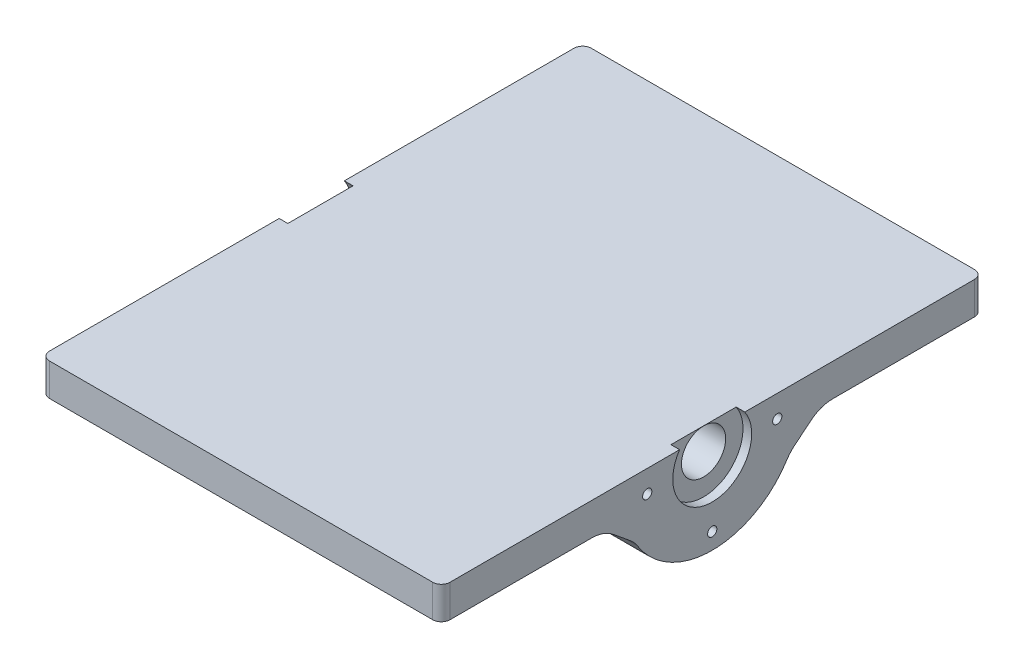
SolidWorks part; units mm, degrees
material "Copper"
ref_plane "Front Plane" through (0, 0, 0) normal (0, 0, 1) x (1, 0, 0)
ref_plane "Top Plane" through (0, 0, 0) normal (0, 1, 0) x (1, 0, 0)
ref_plane "Right Plane" through (0, 0, 0) normal (1, 0, 0) x (0, 0, -1)
sketch "Sketch1" plane through (0, 0, 0) normal (0, 0, 1) x (1, 0, 0)
  line L1 (0, 0) -> (-117.348, 0)
  line L2 (0, 0) -> (0, -38.1)
  line L3 (0, -38.1) -> (-117.348, -38.1)
  line L4 (-117.348, 0) -> (-117.348, -38.1)
  dimension "D1" = 117.348
  dimension "D2" = 38.1
extrude "Boss-Extrude1" add sketch "Sketch1" along normal blind 158.75
sketch "Sketch2" plane through (0, 0, 0) normal (1, 0, 0) x (0, 0, -1)
  line L0 (-79.375, 0) -> (-79.375, -38.1)
  line L1 (-158.75, 0) -> (0, 0) construction
  line L2 (-158.75, -38.1) -> (0, -38.1) construction
  circle A0 centre (-98.425, -6.5024) radius 1.3525
  circle A1 centre (-60.325, -6.5024) radius 1.3526
  circle A2 centre (-79.375, -25.5524) radius 1.3525
  dimension "D1" = 2.7051
  dimension "D2" = 2.7051
  dimension "D8" = 2.7051
  dimension "D3" = 31.5976
  dimension "D4" = 31.5976
  dimension "D5" = 19.05
  dimension "D6" = 19.05
  dimension "D7" = 19.05
extrude "Cut-Extrude1" cut sketch "Sketch2" against normal blind 152.4 contours A0 | L0 A2 | A1
sketch "Sketch3" plane through (0, 0, 0) normal (1, 0, 0) x (0, 0, -1)
  line L0 (-79.375, 0) -> (-79.375, -38.1) construction
  line L1 (-158.75, 0) -> (0, 0) construction
  line L2 (-158.75, -38.1) -> (0, -38.1) construction
  circle A0 centre (-79.375, -6.5024) radius 6.477
  dimension "D1" = 12.954
  dimension "D2" = 31.5976
extrude "Cut-Extrude4" cut sketch "Sketch3" against normal blind 154.686
sketch "Sketch4" plane through (0, 0, 0) normal (1, 0, 0) x (0, 0, -1)
  circle A0 centre (-79.375, -6.5024) radius 11.557
  dimension "D1" = 23.114
extrude "Cut-Extrude5" cut sketch "Sketch4" against normal blind 2.54
ref_plane "Midplane 1" through (-58.674, 0, 0) normal (1, 0, 0) x (0, 0, -1)
mirror "Mirror1" about plane through (-58.674, 0, 0) normal (1, 0, 0) of "Cut-Extrude5"
sketch "Sketch5" plane through (0, 0, 0) normal (1, 0, 0) x (0, 0, -1)
  line L0 (-158.75, -9.525) -> (-104.775, -9.525)
  line L1 (-158.75, -38.1) -> (-158.75, 0) construction
  line L2 (-53.975, -9.525) -> (0, -9.525)
  line L3 (0, -38.1) -> (0, 0) construction
  line L4 (0, -9.525) -> (0, -59.7545)
  line L5 (0, -59.7545) -> (-158.75, -59.7545)
  line L6 (-158.75, -9.525) -> (-158.75, -59.7545)
  line L7 (-69.8208, 0) -> (0, 0) construction
  line L8 (-158.75, 0) -> (-88.9292, 0) construction
  arc A0 (-104.775, -9.525) -> (-53.975, -9.525) centre (-79.375, -4.4197) ccw
  dimension "D1" = 53.975
  dimension "D5" = 25.908
  dimension "D2" = 53.975
  dimension "D3" = 9.525
  dimension "D4" = 9.525
extrude "Cut-Extrude6" cut sketch "Sketch5" against normal blind 254
chamfer "Chamfer1" distance 6.35 2 edges at (-58.674, -9.525, 104.775) (-58.674, -9.525, 53.975)
fillet "Fillet1" radius 10 4 edges at (-58.674, -9.525, 111.125) (-58.674, -16.9616, 102.0449) (-58.674, -16.9616, 56.7051) (-58.674, -9.525, 47.625)
fillet "Fillet2" radius 2.54 4 edges at (0, -4.7625, 158.75) (-117.348, -4.7625, 158.75) (-117.348, -4.7625, 0) (0, -4.7625, 0)
ref_plane "Midplane 2" through (0, 0, 79.375) normal (0, 0, -1) x (-1, 0, 0)
